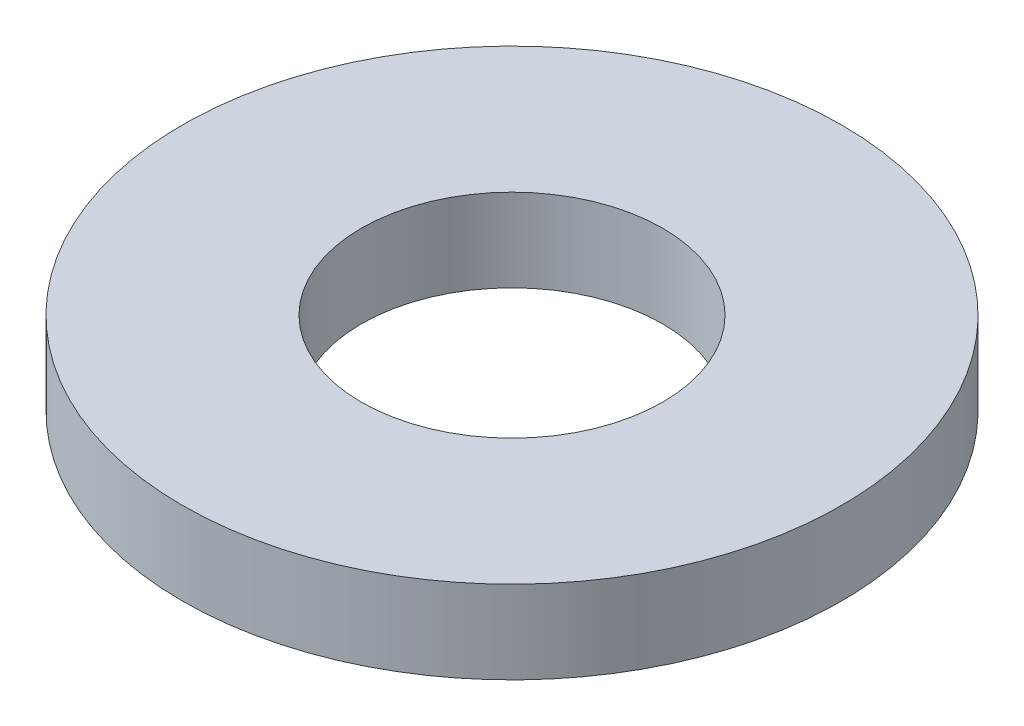
SolidWorks part; units mm, degrees
ref_plane "Front Plane" through (0, 0, 0) normal (0, 0, 1) x (1, 0, 0)
ref_plane "Top Plane" through (0, 0, 0) normal (0, 1, 0) x (1, 0, 0)
ref_plane "Right Plane" through (0, 0, 0) normal (1, 0, 0) x (0, 0, -1)
sketch "Sketch1" plane through (0, 0, 0) normal (0, 1, 0) x (1, 0, 0)
  circle A0 centre (0, 0) radius 87.5
  dimension "FLANGE_OD" = 175
extrude "Boss-Extrude1" add sketch "Sketch1" along normal blind 22
sketch "Sketch2" plane through (0, 0, 0) normal (0, 1, 0) x (1, 0, 0)
  circle A0 centre (0, 0) radius 40
  dimension "BORE_D" = 80
extrude "Cut-Extrude1" cut sketch "Sketch2" along normal through all
sketch "Sketch3" plane through (0, 22, 0) normal (0, 1, 0) x (1, 0, 0)
  circle A0 centre (0, 0) radius 30.5737 construction
  circle A1 centre (-30.5737, 0) radius 6.0685
  dimension "BOLT_D" = 12.137
  dimension "BOLT_PCD" = 61.1474
extrude "Cut-Extrude2" cut sketch "Sketch3" against normal blind 14.8208 rebuild error yes
pattern_circular "CirPattern1" count 5 over 360 rebuild error yes
